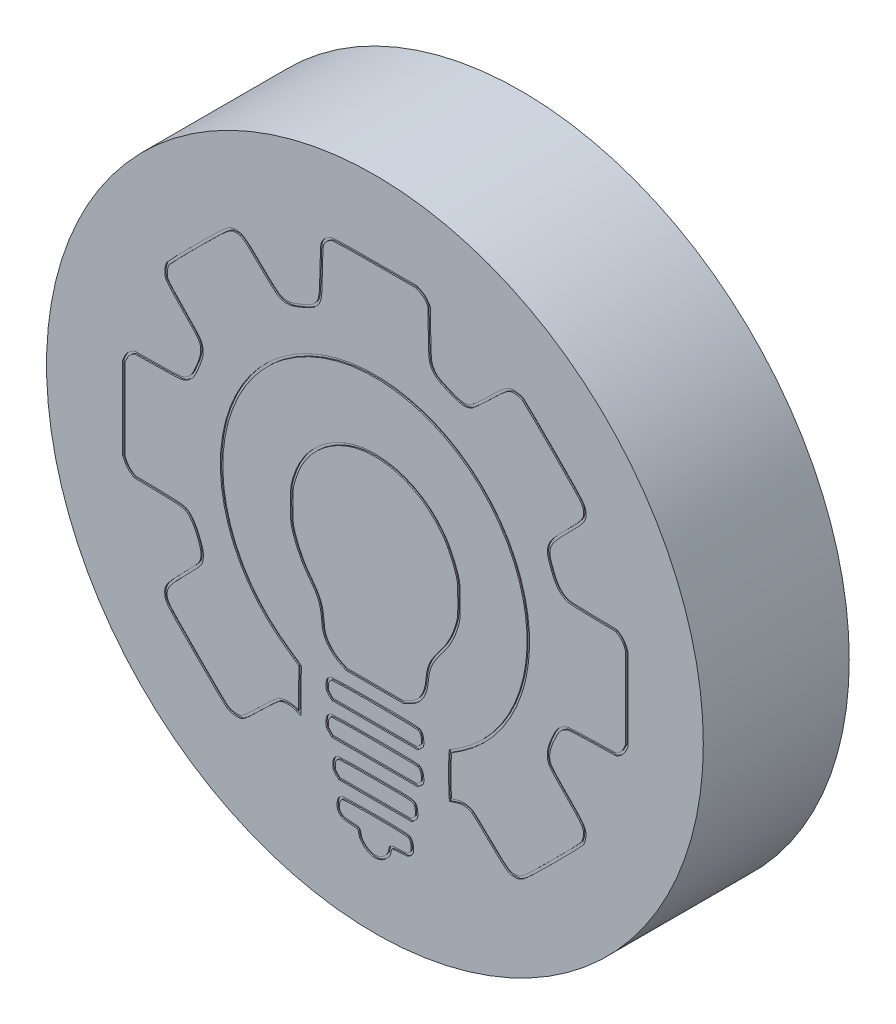
SolidWorks part; units mm, degrees
ref_plane "Front Plane" through (0, 0, 0) normal (0, 0, 1) x (1, 0, 0)
ref_plane "Top Plane" through (0, 0, 0) normal (0, 1, 0) x (1, 0, 0)
ref_plane "Right Plane" through (0, 0, 0) normal (1, 0, 0) x (0, 0, -1)
sketch "Sketch1" plane through (0, 0, 0) normal (0, 0, 1) x (1, 0, 0)
  circle A0 centre (0, 0) radius 25.025
  circle A1 centre (0, 0) radius 27
  dimension "D1" = 50.05
  dimension "D2" = 54
extrude "Boss-Extrude1" add sketch "Sketch1" along normal blind 10
sketch "Sketch2" plane through (0, 0, 10) normal (0, 0, 1) x (1, 0, 0)
  circle A0 centre (0, 0) radius 27
  circle A1 centre (0, 0) radius 27 construction
  point P8 (0, 0)
  circle M3 centre (0, 0) radius 27
  circle M4 centre (0, 0) radius 25.025
extrude "Boss-Extrude3" add sketch "Sketch2" along normal blind 2 contours M3 M4 | M4 region at (-26.2363, 0, 10) region at (0, 0, 10)
sketch "Sketch4" plane through (0, 0, 12) normal (0, 0, 1) x (1, 0, 0)
  line L0 (-17.8576, 4.6203) -> (-19.805, 4.585)
  line L1 (-19.805, 4.585) -> (-20.1013, 4.3874)
  line L2 (-20.574, 3.823) -> (-20.7433, 3.4561)
  line L3 (-20.7433, 3.4561) -> (-20.7433, 0.0624)
  line L4 (-20.7433, 0.0624) -> (-20.7433, -3.3243)
  line L5 (-20.7433, -3.3243) -> (-20.567, -3.6841)
  line L6 (-20.0942, -4.2415) -> (-19.805, -4.4461)
  line L7 (-19.805, -4.4461) -> (-17.8576, -4.4814)
  line L8 (-6.3994, -14.4086) -> (-6.0678, -14.5638)
  line L9 (-6.0678, -14.5638) -> (-6.0678, -12.7999)
  line L10 (17.9282, -4.4884) -> (19.8755, -4.4461)
  line L11 (19.8755, -4.4461) -> (20.1577, -4.2556)
  line L12 (20.6305, -3.6982) -> (20.8139, -3.3243)
  line L13 (20.8139, -3.3243) -> (20.8139, 0.0624)
  line L14 (20.8139, 0.0624) -> (20.8139, 3.4561)
  line L15 (20.8139, 3.4561) -> (20.6446, 3.823)
  line L16 (20.1718, 4.3874) -> (19.8755, 4.585)
  line L17 (19.8755, 4.585) -> (17.9282, 4.6203)
  line L18 (4.5861, 17.9976) -> (4.5508, 19.9097)
  line L19 (4.5508, 19.9097) -> (4.3603, 20.1919)
  line L20 (3.8029, 20.6646) -> (3.429, 20.8481)
  line L21 (3.429, 20.8481) -> (0.0423, 20.841)
  line L22 (-2.8363, -9.2298) -> (-2.3636, -9.4556)
  line L23 (-2.3636, -9.4556) -> (0, -9.4556)
  line L24 (0, -9.4556) -> (2.3636, -9.4556)
  line L25 (2.3636, -9.4556) -> (2.8363, -9.2298)
  line L26 (-3.7818, -11.9321) -> (-3.5419, -12.1719)
  line L27 (-3.5419, -12.1719) -> (-0.0071, -12.1719)
  line L28 (-0.0071, -12.1719) -> (3.5207, -12.1719)
  line L29 (3.5207, -12.1719) -> (3.7747, -11.9532)
  line L30 (-3.7818, -14.5629) -> (-3.5419, -14.8028)
  line L31 (-3.5419, -14.8028) -> (-0.0071, -14.8028)
  line L32 (-0.0071, -14.8028) -> (3.5207, -14.8028)
  line L33 (3.5207, -14.8028) -> (3.7747, -14.5841)
  line L34 (-3.2173, -17.2943) -> (-2.9774, -17.5342)
  line L35 (-2.9774, -17.5342) -> (0.0282, -17.5342)
  line L36 (0.0282, -17.5342) -> (3.0268, -17.5342)
  line L37 (3.0268, -17.5342) -> (3.2808, -17.3155)
  line L76 (-17.854, 4.4203) -> (-19.7428, 4.3861)
  line L77 (-19.7428, 4.3861) -> (-19.989, 4.2219)
  line L78 (-20.3932, 3.7376) -> (-20.5433, 3.4122)
  line L79 (-20.5433, 3.4122) -> (-20.5433, 0.0624)
  line L80 (-20.5433, 0.0624) -> (-20.5433, -3.2779)
  line L81 (-20.5433, -3.2779) -> (-20.3881, -3.5947)
  line L82 (-19.9817, -4.0761) -> (-19.7398, -4.2473)
  line L83 (-19.7398, -4.2473) -> (-17.854, -4.2814)
  line L84 (-6.3165, -14.2265) -> (-6.2678, -14.2493)
  line L85 (-6.2678, -14.2493) -> (-6.2678, -12.7999)
  line L86 (17.9238, -4.2885) -> (19.8124, -4.2474)
  line L87 (19.8124, -4.2474) -> (20.0471, -4.089)
  line L88 (20.4516, -3.6088) -> (20.6139, -3.2779)
  line L89 (20.6139, -3.2779) -> (20.6139, 0.0624)
  line L90 (20.6139, 0.0624) -> (20.6139, 3.4122)
  line L91 (20.6139, 3.4122) -> (20.4637, 3.7376)
  line L92 (20.0596, 4.2219) -> (19.8133, 4.3861)
  line L93 (19.8133, 4.3861) -> (17.9243, 4.4203)
  line L94 (4.3861, 17.9939) -> (4.352, 19.8468)
  line L95 (4.352, 19.8468) -> (4.1937, 20.0812)
  line L96 (3.7135, 20.4857) -> (3.3828, 20.648)
  line L97 (3.3828, 20.648) -> (0.0423, 20.641)
  line L98 (-2.7503, -9.0492) -> (-2.3183, -9.2556)
  line L99 (-2.3183, -9.2556) -> (0, -9.2556)
  line L100 (0, -9.2556) -> (2.3183, -9.2556)
  line L101 (2.3183, -9.2556) -> (2.7507, -9.0491)
  line L102 (-3.6404, -11.7906) -> (-3.459, -11.9719)
  line L103 (-3.459, -11.9719) -> (-0.0071, -11.9719)
  line L104 (-0.0071, -11.9719) -> (3.4465, -11.9719)
  line L105 (3.4465, -11.9719) -> (3.6424, -11.8032)
  line L106 (-3.6404, -14.4215) -> (-3.459, -14.6028)
  line L107 (-3.459, -14.6028) -> (-0.0071, -14.6028)
  line L108 (-0.0071, -14.6028) -> (3.4465, -14.6028)
  line L109 (3.4465, -14.6028) -> (3.6424, -14.4341)
  line L110 (-3.0759, -17.1529) -> (-2.8946, -17.3342)
  line L111 (-2.8946, -17.3342) -> (0.0282, -17.3342)
  line L112 (0.0282, -17.3342) -> (2.9526, -17.3342)
  line L113 (2.9526, -17.3342) -> (3.1485, -17.1655)
  spline S0 degree 3 poles (-3.5631, 20.7634) (-3.8876, 20.6435) (-4.1346, 20.4459) (-4.318, 20.1566) knots 0 0 0 0 1 1 1 1
  spline S1 degree 3 poles (-4.318, 20.1566) (-4.4732, 19.9026) (-4.4803, 19.825) (-4.5156, 17.9906) knots 0 0 0 0 1 1 1 1
  spline S2 degree 3 poles (-4.5156, 17.9906) (-4.5579, 15.888) (-4.5791, 15.7822) (-5.0236, 15.3377) knots 0 0 0 0 1 1 1 1
  spline S3 degree 3 poles (-5.0236, 15.3377) (-5.3128, 15.0413) (-6.5758, 14.4981) (-7.0767, 14.4416) knots 0 0 0 0 1 1 1 1
  spline S4 degree 3 poles (-7.0767, 14.4416) (-7.6976, 14.3781) (-7.9163, 14.5263) (-9.2851, 15.888) knots 0 0 0 0 1 1 1 1
  spline S5 degree 3 poles (-9.2851, 15.888) (-10.5622, 17.158) (-10.8797, 17.3838) (-11.3595, 17.3908) knots 0 0 0 0 1 1 1 1
  spline S6 degree 3 poles (-11.3595, 17.3908) (-12.0086, 17.3908) (-12.0297, 17.3767) (-14.5556, 14.865) knots 0 0 0 0 1 1 1 1
  spline S7 degree 3 poles (-14.5556, 14.865) (-15.868, 13.5526) (-17.0039, 12.3885) (-17.0815, 12.2615) knots 0 0 0 0 1 1 1 1
  spline S8 degree 3 poles (-17.0815, 12.2615) (-17.265, 11.9651) (-17.3285, 11.4148) (-17.2156, 11.0691) knots 0 0 0 0 1 1 1 1
  spline S9 degree 3 poles (-17.2156, 11.0691) (-17.145, 10.8645) (-16.7852, 10.4482) (-15.7974, 9.4463) knots 0 0 0 0 1 1 1 1
  spline S10 degree 3 poles (-15.7974, 9.4463) (-14.3933, 8.0211) (-14.3228, 7.9152) (-14.3228, 7.252) knots 0 0 0 0 1 1 1 1
  spline S11 degree 3 poles (-14.3228, 7.252) (-14.3228, 6.871) (-14.8378, 5.5657) (-15.113, 5.22) knots 0 0 0 0 1 1 1 1
  spline S12 degree 3 poles (-15.113, 5.22) (-15.233, 5.0859) (-15.4587, 4.8954) (-15.614, 4.8108) knots 0 0 0 0 1 1 1 1
  spline S13 degree 3 poles (-15.614, 4.8108) (-15.8962, 4.6697) (-16.0232, 4.6556) (-17.8576, 4.6203) knots 0 0 0 0 1 1 1 1
  spline S14 degree 3 poles (-20.1013, 4.3874) (-20.3059, 4.2463) (-20.4541, 4.077) (-20.574, 3.823) knots 0 0 0 0 1 1 1 1
  spline S15 degree 3 poles (-20.567, -3.6841) (-20.4541, -3.9099) (-20.2777, -4.1216) (-20.0942, -4.2415) knots 0 0 0 0 1 1 1 1
  spline S16 degree 3 poles (-17.8576, -4.4814) (-15.6563, -4.5237) (-15.5857, -4.5378) (-15.1412, -5.0529) knots 0 0 0 0 1 1 1 1
  spline S17 degree 3 poles (-15.1412, -5.0529) (-14.859, -5.3845) (-14.4216, -6.3441) (-14.3298, -6.8591) knots 0 0 0 0 1 1 1 1
  spline S18 degree 3 poles (-14.3298, -6.8591) (-14.2946, -7.0355) (-14.3016, -7.3036) (-14.3369, -7.5012) knots 0 0 0 0 1 1 1 1
  spline S19 degree 3 poles (-14.3369, -7.5012) (-14.4075, -7.8046) (-14.5133, -7.9386) (-15.7057, -9.1381) knots 0 0 0 0 1 1 1 1
  spline S20 degree 3 poles (-15.7057, -9.1381) (-17.0392, -10.4857) (-17.2791, -10.8243) (-17.2861, -11.3182) knots 0 0 0 0 1 1 1 1
  spline S21 degree 3 poles (-17.2861, -11.3182) (-17.2861, -11.9603) (-17.2579, -11.9956) (-14.7532, -14.5215) knots 0 0 0 0 1 1 1 1
  spline S22 degree 3 poles (-14.7532, -14.5215) (-13.4479, -15.8338) (-12.2837, -16.9697) (-12.1567, -17.0473) knots 0 0 0 0 1 1 1 1
  spline S23 degree 3 poles (-12.1567, -17.0473) (-11.8604, -17.2308) (-11.3101, -17.2943) (-10.9643, -17.1814) knots 0 0 0 0 1 1 1 1
  spline S24 degree 3 poles (-10.9643, -17.1814) (-10.7597, -17.1179) (-10.3576, -16.7651) (-9.3839, -15.8056) knots 0 0 0 0 1 1 1 1
  spline S25 degree 3 poles (-9.3839, -15.8056) (-8.6642, -15.1) (-7.9657, -14.458) (-7.8317, -14.3874) knots 0 0 0 0 1 1 1 1
  spline S26 degree 3 poles (-7.8317, -14.3874) (-7.4859, -14.204) (-6.8298, -14.2181) (-6.3994, -14.4086) knots 0 0 0 0 1 1 1 1
  spline S27 degree 3 poles (-6.0678, -12.7999) (-6.0678, -11.8333) (-6.0607, -11.0219) (-6.0537, -10.9866) knots 0 0 0 0 1 1 1 1
  spline S28 degree 3 poles (-6.0537, -10.9866) (-6.0537, -10.9584) (-6.4135, -10.6903) (-6.8651, -10.3869) knots 0 0 0 0 1 1 1 1
  spline S29 degree 3 poles (-6.8651, -10.3869) (-9.3133, -8.75) (-10.9785, -6.5769) (-11.8816, -3.8393) knots 0 0 0 0 1 1 1 1
  spline S30 degree 3 poles (-11.8816, -3.8393) (-13.5608, 1.2195) (-11.7969, 6.864) (-7.5424, 10.0672) knots 0 0 0 0 1 1 1 1
  spline S31 degree 3 poles (-7.5424, 10.0672) (-3.3796, 13.1928) (2.2366, 13.4327) (6.6675, 10.6669) knots 0 0 0 0 1 1 1 1
  spline S32 degree 3 poles (6.6675, 10.6669) (11.5006, 7.6542) (13.6807, 1.6217) (11.8886, -3.8111) knots 0 0 0 0 1 1 1 1
  spline S33 degree 3 poles (11.8886, -3.8111) (11.0067, -6.5063) (9.2992, -8.7571) (6.9427, -10.3375) knots 0 0 0 0 1 1 1 1
  spline S34 degree 3 poles (6.9427, -10.3375) (6.5476, -10.5986) (6.1948, -10.8243) (6.1454, -10.8384) knots 0 0 0 0 1 1 1 1
  spline S35 degree 3 poles (6.1454, -10.8384) (6.0184, -10.8808) (6.0254, -14.5426) (6.1524, -14.5215) knots 0 0 0 0 1 1 1 1
  spline S36 degree 3 poles (6.1524, -14.5215) (6.2018, -14.5144) (6.4347, -14.4368) (6.6675, -14.3592) knots 0 0 0 0 1 1 1 1
  spline S37 degree 3 poles (6.6675, -14.3592) (7.1261, -14.1898) (7.5424, -14.211) (7.9375, -14.4086) knots 0 0 0 0 1 1 1 1
  spline S38 degree 3 poles (7.9375, -14.4086) (8.0504, -14.4721) (8.7207, -15.0859) (9.4192, -15.7773) knots 0 0 0 0 1 1 1 1
  spline S39 degree 3 poles (9.4192, -15.7773) (10.7033, -17.0473) (10.9855, -17.252) (11.4371, -17.252) knots 0 0 0 0 1 1 1 1
  spline S40 degree 3 poles (11.4371, -17.252) (12.065, -17.252) (12.1144, -17.2167) (14.6262, -14.719) knots 0 0 0 0 1 1 1 1
  spline S41 degree 3 poles (14.6262, -14.719) (15.9385, -13.4137) (17.0745, -12.2496) (17.1521, -12.1226) knots 0 0 0 0 1 1 1 1
  spline S42 degree 3 poles (17.1521, -12.1226) (17.2297, -12.0026) (17.3073, -11.7416) (17.3355, -11.544) knots 0 0 0 0 1 1 1 1
  spline S43 degree 3 poles (17.3355, -11.544) (17.4131, -10.8878) (17.272, -10.6762) (15.8538, -9.2509) knots 0 0 0 0 1 1 1 1
  spline S44 degree 3 poles (15.8538, -9.2509) (15.106, -8.5031) (14.5415, -7.8751) (14.478, -7.734) knots 0 0 0 0 1 1 1 1
  spline S45 degree 3 poles (14.478, -7.734) (14.2946, -7.2966) (14.344, -6.845) (14.6403, -6.1042) knots 0 0 0 0 1 1 1 1
  spline S46 degree 3 poles (14.6403, -6.1042) (15.0354, -5.1305) (15.2471, -4.8553) (15.8045, -4.6084) knots 0 0 0 0 1 1 1 1
  spline S47 degree 3 poles (15.8045, -4.6084) (15.9103, -4.559) (16.7287, -4.5096) (17.9282, -4.4884) knots 0 0 0 0 1 1 1 1
  spline S48 degree 3 poles (20.1577, -4.2556) (20.3412, -4.1357) (20.5105, -3.9381) (20.6305, -3.6982) knots 0 0 0 0 1 1 1 1
  spline S49 degree 3 poles (20.6446, 3.823) (20.5246, 4.077) (20.3765, 4.2463) (20.1718, 4.3874) knots 0 0 0 0 1 1 1 1
  spline S50 degree 3 poles (17.9282, 4.6203) (16.0937, 4.6556) (15.9667, 4.6697) (15.6845, 4.8108) knots 0 0 0 0 1 1 1 1
  spline S51 degree 3 poles (15.6845, 4.8108) (15.2612, 5.0366) (15.0142, 5.3823) (14.6826, 6.2078) knots 0 0 0 0 1 1 1 1
  spline S52 degree 3 poles (14.6826, 6.2078) (14.1393, 7.5766) (14.2311, 7.8306) (15.9103, 9.4886) knots 0 0 0 0 1 1 1 1
  spline S53 degree 3 poles (15.9103, 9.4886) (17.1168, 10.681) (17.3496, 10.9985) (17.3567, 11.4571) knots 0 0 0 0 1 1 1 1
  spline S54 degree 3 poles (17.3567, 11.4571) (17.3567, 12.0992) (17.3285, 12.1345) (14.8237, 14.6603) knots 0 0 0 0 1 1 1 1
  spline S55 degree 3 poles (14.8237, 14.6603) (13.5185, 15.9727) (12.3543, 17.1086) (12.2273, 17.1862) knots 0 0 0 0 1 1 1 1
  spline S56 degree 3 poles (12.2273, 17.1862) (12.1073, 17.2638) (11.8463, 17.3415) (11.6487, 17.3697) knots 0 0 0 0 1 1 1 1
  spline S57 degree 3 poles (11.6487, 17.3697) (10.9926, 17.4473) (10.7668, 17.3062) (9.3486, 15.9021) knots 0 0 0 0 1 1 1 1
  spline S58 degree 3 poles (9.3486, 15.9021) (8.5725, 15.1401) (7.9728, 14.6039) (7.8105, 14.5333) knots 0 0 0 0 1 1 1 1
  spline S59 degree 3 poles (7.8105, 14.5333) (7.3801, 14.357) (7.0203, 14.3993) (6.1807, 14.745) knots 0 0 0 0 1 1 1 1
  spline S60 degree 3 poles (6.1807, 14.745) (5.2564, 15.126) (5.0024, 15.3024) (4.7907, 15.7469) knots 0 0 0 0 1 1 1 1
  spline S61 degree 3 poles (4.7907, 15.7469) (4.6284, 16.0715) (4.6214, 16.1702) (4.5861, 17.9976) knots 0 0 0 0 1 1 1 1
  spline S62 degree 3 poles (4.3603, 20.1919) (4.2404, 20.3753) (4.0428, 20.5447) (3.8029, 20.6646) knots 0 0 0 0 1 1 1 1
  spline S63 degree 3 poles (0.0423, 20.841) (-2.1661, 20.841) (-3.429, 20.8128) (-3.5631, 20.7634) knots 0 0 0 0 1 1 1 1
  spline S64 degree 3 poles (-1.0231, 7.0827) (-2.8998, 6.8146) (-4.7413, 5.6363) (-5.8279, 4.0135) knots 0 0 0 0 1 1 1 1
  spline S65 degree 3 poles (-5.8279, 4.0135) (-6.2653, 3.3503) (-6.4911, 2.8705) (-6.7522, 2.0168) knots 0 0 0 0 1 1 1 1
  spline S66 degree 3 poles (-6.7522, 2.0168) (-6.9286, 1.4523) (-6.9427, 1.3183) (-6.9427, 0.1047) knots 0 0 0 0 1 1 1 1
  spline S67 degree 3 poles (-6.9427, 0.1047) (-6.9427, -1.1229) (-6.9286, -1.2429) (-6.7522, -1.8285) knots 0 0 0 0 1 1 1 1
  spline S68 degree 3 poles (-6.7522, -1.8285) (-6.5052, -2.6258) (-5.9619, -3.6841) (-5.5174, -4.2344) knots 0 0 0 0 1 1 1 1
  spline S69 degree 3 poles (-5.5174, -4.2344) (-4.6849, -5.2787) (-4.4732, -5.7584) (-4.3815, -6.8591) knots 0 0 0 0 1 1 1 1
  spline S70 degree 3 poles (-4.3815, -6.8591) (-4.3392, -7.4165) (-4.2827, -7.6634) (-4.1346, -7.9668) knots 0 0 0 0 1 1 1 1
  spline S71 degree 3 poles (-4.1346, -7.9668) (-3.8664, -8.5101) (-3.4008, -8.9617) (-2.8363, -9.2298) knots 0 0 0 0 1 1 1 1
  spline S72 degree 3 poles (2.8363, -9.2298) (3.7959, -8.7782) (4.2827, -8.0374) (4.3886, -6.8662) knots 0 0 0 0 1 1 1 1
  spline S73 degree 3 poles (4.3886, -6.8662) (4.4873, -5.7937) (4.699, -5.3351) (5.6797, -4.0933) knots 0 0 0 0 1 1 1 1
  spline S74 degree 3 poles (5.6797, -4.0933) (6.1454, -3.5007) (6.5546, -2.6963) (6.8157, -1.8356) knots 0 0 0 0 1 1 1 1
  spline S75 degree 3 poles (6.8157, -1.8356) (6.9991, -1.2358) (7.0132, -1.1229) (7.0132, 0.1047) knots 0 0 0 0 1 1 1 1
  spline S76 degree 3 poles (7.0132, 0.1047) (7.0132, 1.3253) (6.9991, 1.4523) (6.8227, 2.0309) knots 0 0 0 0 1 1 1 1
  spline S77 degree 3 poles (6.8227, 2.0309) (6.5899, 2.7858) (6.1242, 3.7313) (5.6938, 4.3098) knots 0 0 0 0 1 1 1 1
  spline S78 degree 3 poles (5.6938, 4.3098) (4.1698, 6.3771) (1.5663, 7.4496) (-1.0231, 7.0827) knots 0 0 0 0 1 1 1 1
  spline S79 degree 3 poles (-3.6336, -10.5633) (-3.9088, -10.7114) (-4.0217, -10.9231) (-4.0217, -11.3112) knots 0 0 0 0 1 1 1 1
  spline S80 degree 3 poles (-4.0217, -11.3112) (-4.0217, -11.6498) (-3.9934, -11.7204) (-3.7818, -11.9321) knots 0 0 0 0 1 1 1 1
  spline S81 degree 3 poles (3.7747, -11.9532) (3.9934, -11.7557) (4.0217, -11.6992) (4.0217, -11.3817) knots 0 0 0 0 1 1 1 1
  spline S82 degree 3 poles (4.0217, -11.3817) (4.0217, -10.9654) (3.8876, -10.6762) (3.6336, -10.5633) knots 0 0 0 0 1 1 1 1
  spline S83 degree 3 poles (3.6336, -10.5633) (3.3867, -10.4504) (-3.429, -10.4433) (-3.6336, -10.5633) knots 0 0 0 0 1 1 1 1
  spline S84 degree 3 poles (-3.6336, -13.1941) (-3.9088, -13.3423) (-4.0217, -13.554) (-4.0217, -13.942) knots 0 0 0 0 1 1 1 1
  spline S85 degree 3 poles (-4.0217, -13.942) (-4.0217, -14.2807) (-3.9934, -14.3513) (-3.7818, -14.5629) knots 0 0 0 0 1 1 1 1
  spline S86 degree 3 poles (3.7747, -14.5841) (3.9934, -14.3865) (4.0217, -14.3301) (4.0217, -14.0126) knots 0 0 0 0 1 1 1 1
  spline S87 degree 3 poles (4.0217, -14.0126) (4.0217, -13.6104) (3.8664, -13.3) (3.6195, -13.1871) knots 0 0 0 0 1 1 1 1
  spline S88 degree 3 poles (3.6195, -13.1871) (3.3796, -13.0813) (-3.4361, -13.0813) (-3.6336, -13.1941) knots 0 0 0 0 1 1 1 1
  spline S89 degree 3 poles (-3.0692, -15.9255) (-3.3443, -16.0737) (-3.4572, -16.2853) (-3.4572, -16.6734) knots 0 0 0 0 1 1 1 1
  spline S90 degree 3 poles (-3.4572, -16.6734) (-3.4572, -17.0121) (-3.429, -17.0826) (-3.2173, -17.2943) knots 0 0 0 0 1 1 1 1
  spline S91 degree 3 poles (3.2808, -17.3155) (3.4996, -17.1179) (3.5278, -17.0544) (3.5278, -16.751) knots 0 0 0 0 1 1 1 1
  spline S92 degree 3 poles (3.5278, -16.751) (3.5278, -16.5676) (3.4925, -16.3277) (3.4431, -16.2289) knots 0 0 0 0 1 1 1 1
  spline S93 degree 3 poles (3.4431, -16.2289) (3.2667, -15.8479) (3.2173, -15.8408) (0.0212, -15.8408) knots 0 0 0 0 1 1 1 1
  spline S94 degree 3 poles (0.0212, -15.8408) (-1.9897, -15.8479) (-2.9704, -15.8691) (-3.0692, -15.9255) knots 0 0 0 0 1 1 1 1
  spline S95 degree 3 poles (-2.7376, -18.6137) (-2.9845, -18.7548) (-3.1044, -18.9735) (-3.1115, -19.3122) knots 0 0 0 0 1 1 1 1
  spline S96 degree 3 poles (-3.1115, -19.3122) (-3.1256, -19.6508) (-3.0551, -19.8272) (-2.8222, -20.0389) knots 0 0 0 0 1 1 1 1
  spline S97 degree 3 poles (-2.8222, -20.0389) (-2.7023, -20.1518) (-2.5329, -20.1871) (-2.0249, -20.2153) knots 0 0 0 0 1 1 1 1
  spline S98 degree 3 poles (-2.0249, -20.2153) (-1.4464, -20.2435) (-1.3758, -20.2647) (-1.3547, -20.3917) knots 0 0 0 0 1 1 1 1
  spline S99 degree 3 poles (-1.3547, -20.3917) (-1.3053, -20.7515) (-1.2559, -20.8644) (-1.0372, -21.1043) knots 0 0 0 0 1 1 1 1
  spline S100 degree 3 poles (-1.0372, -21.1043) (-0.4516, -21.7816) (0.4516, -21.7816) (1.0372, -21.1043) knots 0 0 0 0 1 1 1 1
  spline S101 degree 3 poles (1.0372, -21.1043) (1.2559, -20.8644) (1.3053, -20.7515) (1.3547, -20.3917) knots 0 0 0 0 1 1 1 1
  spline S102 degree 3 poles (1.3547, -20.3917) (1.3758, -20.2647) (1.4464, -20.2506) (2.0602, -20.2153) knots 0 0 0 0 1 1 1 1
  spline S103 degree 3 poles (2.0602, -20.2153) (2.6952, -20.18) (2.7587, -20.1659) (2.9563, -19.9754) knots 0 0 0 0 1 1 1 1
  spline S104 degree 3 poles (2.9563, -19.9754) (3.1397, -19.799) (3.175, -19.7143) (3.175, -19.4321) knots 0 0 0 0 1 1 1 1
  spline S105 degree 3 poles (3.175, -19.4321) (3.175, -19.0088) (3.0621, -18.7477) (2.8152, -18.6207) knots 0 0 0 0 1 1 1 1
  spline S106 degree 3 poles (2.8152, -18.6207) (2.5471, -18.4867) (-2.4906, -18.4796) (-2.7376, -18.6137) knots 0 0 0 0 1 1 1 1
  spline S107 degree 1 poles (-19.989, 4.2219) (-20.3932, 3.7376) knots 0 0 1 1 construction
  spline S108 degree 1 poles (-20.3881, -3.5947) (-19.9817, -4.0761) knots 0 0 1 1 construction
  spline S109 degree 1 poles (-17.854, -4.2814) (-14.9894, -4.9227) knots 0 0 1 1 construction
  spline S110 degree 1 poles (-14.9894, -4.9227) (-14.1333, -6.822) knots 0 0 1 1 construction
  spline S111 degree 1 poles (-14.1333, -6.822) (-14.1409, -7.5414) knots 0 0 1 1 construction
  spline S112 degree 1 poles (-14.1409, -7.5414) (-15.5637, -9.2789) knots 0 0 1 1 construction
  spline S113 degree 1 poles (-15.5637, -9.2789) (-17.0861, -11.3197) knots 0 0 1 1 construction
  spline S114 degree 1 poles (-17.0861, -11.3197) (-14.6113, -14.3805) knots 0 0 1 1 construction
  spline S115 degree 1 poles (-14.6113, -14.3805) (-12.0501, -16.8781) knots 0 0 1 1 construction
  spline S116 degree 1 poles (-12.0501, -16.8781) (-11.025, -16.9908) knots 0 0 1 1 construction
  spline S117 degree 1 poles (-11.025, -16.9908) (-9.5241, -15.6629) knots 0 0 1 1 construction
  spline S118 degree 1 poles (-9.5241, -15.6629) (-7.9252, -14.2106) knots 0 0 1 1 construction
  spline S119 degree 1 poles (-7.9252, -14.2106) (-6.3165, -14.2265) knots 0 0 1 1 construction
  spline S120 degree 1 poles (-6.2678, -12.7999) (-6.2573, -11.0672) knots 0 0 1 1 construction
  spline S121 degree 1 poles (-6.2573, -11.0672) (-6.9764, -10.553) knots 0 0 1 1 construction
  spline S122 degree 1 poles (-6.9764, -10.553) (-12.0714, -3.9022) knots 0 0 1 1 construction
  spline S123 degree 1 poles (-12.0714, -3.9022) (-7.6626, 10.227) knots 0 0 1 1 construction
  spline S124 degree 1 poles (-7.6626, 10.227) (6.7734, 10.8366) knots 0 0 1 1 construction
  spline S125 degree 1 poles (6.7734, 10.8366) (12.0786, -3.8735) knots 0 0 1 1 construction
  spline S126 degree 1 poles (12.0786, -3.8735) (7.0535, -10.504) knots 0 0 1 1 construction
  spline S127 degree 1 poles (7.0535, -10.504) (6.3095, -10.9791) knots 0 0 1 1 construction
  spline S128 degree 1 poles (6.3095, -10.9791) (6.3008, -14.2697) knots 0 0 1 1 construction
  spline S129 degree 1 poles (6.3008, -14.2697) (6.6013, -14.1704) knots 0 0 1 1 construction
  spline S130 degree 1 poles (6.6013, -14.1704) (8.0313, -14.2319) knots 0 0 1 1 construction
  spline S131 degree 1 poles (8.0313, -14.2319) (9.5598, -15.6352) knots 0 0 1 1 construction
  spline S132 degree 1 poles (9.5598, -15.6352) (11.4371, -17.052) knots 0 0 1 1 construction
  spline S133 degree 1 poles (11.4371, -17.052) (14.4851, -14.5772) knots 0 0 1 1 construction
  spline S134 degree 1 poles (14.4851, -14.5772) (16.9828, -12.0161) knots 0 0 1 1 construction
  spline S135 degree 1 poles (16.9828, -12.0161) (17.1372, -11.5181) knots 0 0 1 1 construction
  spline S136 degree 1 poles (17.1372, -11.5181) (15.7122, -9.3922) knots 0 0 1 1 construction
  spline S137 degree 1 poles (15.7122, -9.3922) (14.2946, -7.8137) knots 0 0 1 1 construction
  spline S138 degree 1 poles (14.2946, -7.8137) (14.4548, -6.0294) knots 0 0 1 1 construction
  spline S139 degree 1 poles (14.4548, -6.0294) (15.7222, -4.4261) knots 0 0 1 1 construction
  spline S140 degree 1 poles (15.7222, -4.4261) (17.9238, -4.2885) knots 0 0 1 1 construction
  spline S141 degree 1 poles (20.0471, -4.089) (20.4516, -3.6088) knots 0 0 1 1 construction
  spline S142 degree 1 poles (20.4637, 3.7376) (20.0596, 4.2219) knots 0 0 1 1 construction
  spline S143 degree 1 poles (17.9243, 4.4203) (15.5927, 4.6331) knots 0 0 1 1 construction
  spline S144 degree 1 poles (15.5927, 4.6331) (14.4969, 6.1336) knots 0 0 1 1 construction
  spline S145 degree 1 poles (14.4969, 6.1336) (15.7697, 9.6309) knots 0 0 1 1 construction
  spline S146 degree 1 poles (15.7697, 9.6309) (17.1567, 11.4587) knots 0 0 1 1 construction
  spline S147 degree 1 poles (17.1567, 11.4587) (14.6818, 14.5194) knots 0 0 1 1 construction
  spline S148 degree 1 poles (14.6818, 14.5194) (12.1208, 17.0169) knots 0 0 1 1 construction
  spline S149 degree 1 poles (12.1208, 17.0169) (11.6228, 17.1714) knots 0 0 1 1 construction
  spline S150 degree 1 poles (11.6228, 17.1714) (9.489, 15.7597) knots 0 0 1 1 construction
  spline S151 degree 1 poles (9.489, 15.7597) (7.8883, 14.3491) knots 0 0 1 1 construction
  spline S152 degree 1 poles (7.8883, 14.3491) (6.1045, 14.5601) knots 0 0 1 1 construction
  spline S153 degree 1 poles (6.1045, 14.5601) (4.611, 15.6592) knots 0 0 1 1 construction
  spline S154 degree 1 poles (4.611, 15.6592) (4.3861, 17.9939) knots 0 0 1 1 construction
  spline S155 degree 1 poles (4.1937, 20.0812) (3.7135, 20.4857) knots 0 0 1 1 construction
  spline S156 degree 1 poles (0.0423, 20.641) (-3.4992, 20.5738) knots 0 0 1 1 construction
  spline S157 degree 1 poles (-3.4992, 20.5738) (-4.1482, 20.0509) knots 0 0 1 1 construction
  spline S158 degree 1 poles (-4.1482, 20.0509) (-4.3156, 17.9866) knots 0 0 1 1 construction
  spline S159 degree 1 poles (-4.3156, 17.9866) (-4.8814, 15.197) knots 0 0 1 1 construction
  spline S160 degree 1 poles (-4.8814, 15.197) (-7.0554, 14.2428) knots 0 0 1 1 construction
  spline S161 degree 1 poles (-7.0554, 14.2428) (-9.4262, 15.7462) knots 0 0 1 1 construction
  spline S162 degree 1 poles (-9.4262, 15.7462) (-11.361, 17.1908) knots 0 0 1 1 construction
  spline S163 degree 1 poles (-11.361, 17.1908) (-14.4144, 14.7233) knots 0 0 1 1 construction
  spline S164 degree 1 poles (-14.4144, 14.7233) (-16.9123, 12.1549) knots 0 0 1 1 construction
  spline S165 degree 1 poles (-16.9123, 12.1549) (-17.026, 11.1329) knots 0 0 1 1 construction
  spline S166 degree 1 poles (-17.026, 11.1329) (-15.655, 9.5867) knots 0 0 1 1 construction
  spline S167 degree 1 poles (-15.655, 9.5867) (-14.1228, 7.252) knots 0 0 1 1 construction
  spline S168 degree 1 poles (-14.1228, 7.252) (-14.9601, 5.0909) knots 0 0 1 1 construction
  spline S169 degree 1 poles (-14.9601, 5.0909) (-15.5213, 4.6335) knots 0 0 1 1 construction
  spline S170 degree 1 poles (-15.5213, 4.6335) (-17.854, 4.4203) knots 0 0 1 1 construction
  spline S171 degree 3 poles (-19.989, 4.2219) (-20.0319, 4.1923) (-20.1163, 4.1267) (-20.2192, 4.0206) (-20.3099, 3.8978) (-20.3682, 3.7904) (-20.3932, 3.7376) knots 0.002323 0.002323 0.002323 0.002323 0.251742 0.501161 0.750581 1 1 1 1
  spline S172 degree 3 poles (-20.3881, -3.5947) (-20.363, -3.6448) (-20.3067, -3.7417) (-20.2049, -3.8781) (-20.0918, -3.9953) (-20.0211, -4.0504) (-19.9817, -4.0761) knots 0 0 0 0 0.25139 0.502779 0.754169 1.005559 1.005559 1.005559 1.005559
  spline S173 degree 3 poles (-17.854, -4.2814) (-17.7244, -4.2839) (-17.4538, -4.2892) (-17.0029, -4.2994) (-16.534, -4.3146) (-16.111, -4.3432) (-15.6809, -4.404) (-15.304, -4.5609) (-15.0925, -4.8032) (-14.9894, -4.9227) knots -0.000034 -0.000034 -0.000034 -0.000034 0.062489 0.125013 0.250059 0.375105 0.500152 0.750245 1.000338 1.000338 1.000338 1.000338
  spline S174 degree 3 poles (-14.9894, -4.9227) (-14.9436, -4.9766) (-14.8652, -5.0844) (-14.6914, -5.3691) (-14.4773, -5.7943) (-14.2524, -6.3571) (-14.1628, -6.6573) (-14.1333, -6.822) knots -0.000527 -0.000527 -0.000527 -0.000527 0.124393 0.249313 0.499154 0.748994 0.998835 0.998835 0.998835 0.998835
  spline S175 degree 3 poles (-14.1333, -6.822) (-14.122, -6.8791) (-14.1088, -6.9924) (-14.1045, -7.1793) (-14.1152, -7.3686) (-14.1305, -7.4833) (-14.1409, -7.5414) knots 0.003226 0.003226 0.003226 0.003226 0.25457 0.505915 0.757259 1.008604 1.008604 1.008604 1.008604
  spline S176 degree 3 poles (-14.1409, -7.5414) (-14.1619, -7.6318) (-14.2122, -7.7972) (-14.3793, -8.0379) (-14.6058, -8.2954) (-14.8383, -8.5424) (-15.0974, -8.808) (-15.3454, -9.0591) (-15.4928, -9.2076) (-15.5637, -9.2789) knots -0.005543 -0.005543 -0.005543 -0.005543 0.245831 0.497206 0.622893 0.74858 0.874267 0.937111 0.999954 0.999954 0.999954 0.999954
  spline S177 degree 3 poles (-15.5637, -9.2789) (-15.6427, -9.3587) (-15.806, -9.5245) (-16.0852, -9.8118) (-16.3807, -10.1244) (-16.6485, -10.4272) (-16.9062, -10.7551) (-17.0599, -11.0361) (-17.0846, -11.2203) (-17.0861, -11.3197) knots 0.000041 0.000041 0.000041 0.000041 0.062471 0.124902 0.249763 0.374624 0.499485 0.749207 0.998929 0.998929 0.998929 0.998929
  spline S178 degree 3 poles (-17.0861, -11.3197) (-17.0861, -11.3867) (-17.0844, -11.5355) (-17.0592, -11.6701) (-16.9879, -11.8353) (-16.8223, -12.0734) (-16.5312, -12.4124) (-16.0911, -12.8797) (-15.5728, -13.4093) (-15.0654, -13.9225) (-14.7582, -14.2323) (-14.6113, -14.3805) knots 0.000773 0.000773 0.000773 0.000773 0.125675 0.250576 0.375478 0.50038 0.625281 0.750183 0.875084 0.937535 0.999986 0.999986 0.999986 0.999986
  spline S179 degree 3 poles (-14.6113, -14.3805) (-14.3067, -14.6867) (-13.6667, -15.3261) (-13.0066, -15.9757) (-12.5759, -16.3931) (-12.3149, -16.6415) (-12.1607, -16.7842) (-12.074, -16.8594) (-12.0611, -16.8702) (-12.0501, -16.8781) knots 0.000027 0.000027 0.000027 0.000027 0.244111 0.488195 0.610236 0.732278 0.85432 0.915341 0.976362 0.976362 0.976362 0.976362
  spline S180 degree 3 poles (-12.0501, -16.8781) (-11.9834, -16.9192) (-11.8494, -16.974) (-11.556, -17.0367) (-11.2541, -17.0412) (-11.1028, -17.0162) (-11.025, -16.9908) knots 0.002003 0.002003 0.002003 0.002003 0.251839 0.501675 0.751511 1.001347 1.001347 1.001347 1.001347
  spline S181 degree 3 poles (-11.025, -16.9908) (-11.0073, -16.9853) (-10.9841, -16.9752) (-10.8573, -16.8986) (-10.6225, -16.7104) (-10.2529, -16.3709) (-9.8754, -16.0078) (-9.6367, -15.7739) (-9.5241, -15.6629) knots -0.002287 -0.002287 -0.002287 -0.002287 0.123007 0.248301 0.498888 0.749476 0.87477 1.000063 1.000063 1.000063 1.000063
  spline S182 degree 3 poles (-9.5241, -15.6629) (-9.3489, -15.4912) (-8.9825, -15.1373) (-8.5061, -14.6923) (-8.1964, -14.4159) (-8.0233, -14.2751) (-7.9624, -14.2302) (-7.9252, -14.2106) knots -0.000086 -0.000086 -0.000086 -0.000086 0.249847 0.499779 0.749712 0.874679 0.999645 0.999645 0.999645 0.999645
  spline S183 degree 3 poles (-7.9252, -14.2106) (-7.8113, -14.1502) (-7.5674, -14.0766) (-7.1446, -14.0447) (-6.7091, -14.0913) (-6.4437, -14.1702) (-6.3165, -14.2265) knots 0.000189 0.000189 0.000189 0.000189 0.250515 0.500841 0.751167 1.001494 1.001494 1.001494 1.001494
  spline S184 degree 3 poles (-6.2678, -12.7999) (-6.2678, -12.6085) (-6.2672, -12.2098) (-6.2648, -11.7068) (-6.262, -11.3729) (-6.2593, -11.169) (-6.2581, -11.1043) (-6.2573, -11.0672) knots 0 0 0 0 0.206567 0.413133 0.6197 0.722983 0.826266 0.826266 0.826266 0.826266
  spline S185 degree 3 poles (-6.2573, -11.0672) (-6.2956, -11.0361) (-6.3621, -10.985) (-6.536, -10.8573) (-6.7384, -10.7147) (-6.8988, -10.6052) (-6.9764, -10.553) knots 0.27751 0.27751 0.27751 0.27751 0.458097 0.638685 0.819273 0.99986 0.99986 0.99986 0.99986
  spline S186 degree 3 poles (-6.9764, -10.553) (-7.5808, -10.149) (-8.7469, -9.2354) (-10.1592, -7.682) (-11.2854, -5.9214) (-11.8473, -4.5815) (-12.0714, -3.9022) knots 0.000025 0.000025 0.000025 0.000025 0.250014 0.500002 0.749991 0.999979 0.999979 0.999979 0.999979
  spline S187 degree 3 poles (-12.0714, -3.9022) (-12.2822, -3.2671) (-12.6031, -1.9523) (-12.8135, 0.6761) (-12.3171, 3.9287) (-10.8751, 6.8855) (-9.2077, 8.9267) (-8.1968, 9.8249) (-7.6626, 10.227) knots 0.000011 0.000011 0.000011 0.000011 0.125011 0.250011 0.50001 0.750009 0.875009 1.000008 1.000008 1.000008 1.000008
  spline S188 degree 3 poles (-7.6626, 10.227) (-7.1409, 10.6187) (-6.0277, 11.3284) (-3.6829, 12.3608) (-0.5551, 12.9641) (2.6154, 12.6276) (5.0448, 11.7967) (6.2183, 11.183) (6.7734, 10.8366) knots -0.000008 -0.000008 -0.000008 -0.000008 0.124992 0.249993 0.499994 0.749995 0.874996 0.999996 0.999996 0.999996 0.999996
  spline S189 degree 3 poles (6.7734, 10.8366) (7.3791, 10.459) (8.5348, 9.5901) (10.4582, 7.5449) (12.1619, 4.4806) (12.809, 1.0303) (12.6368, -1.7799) (12.3031, -3.193) (12.0786, -3.8735) knots 0.000004 0.000004 0.000004 0.000004 0.125001 0.249999 0.499995 0.749991 0.874988 0.999986 0.999986 0.999986 0.999986
  spline S190 degree 3 poles (12.0786, -3.8735) (11.8576, -4.5489) (11.3009, -5.8741) (10.174, -7.6485) (8.7696, -9.2131) (7.6439, -10.108) (7.0535, -10.504) knots 0.000028 0.000028 0.000028 0.000028 0.250041 0.500054 0.750068 1.000081 1.000081 1.000081 1.000081
  spline S191 degree 3 poles (7.0535, -10.504) (6.9768, -10.5547) (6.8177, -10.6592) (6.6101, -10.7936) (6.4284, -10.9082) (6.3536, -10.9539) (6.3095, -10.9791) knots -0.000485 -0.000485 -0.000485 -0.000485 0.199236 0.398958 0.598679 0.7984 0.7984 0.7984 0.7984
  spline S192 degree 3 poles (6.3095, -10.9791) (6.3045, -11.0135) (6.2979, -11.0732) (6.2823, -11.2686) (6.268, -11.5801) (6.2569, -12.0396) (6.2526, -12.5435) (6.2548, -13.0569) (6.2636, -13.5447) (6.276, -13.8967) (6.2896, -14.1338) (6.2963, -14.2219) (6.3008, -14.2697) knots 0.098872 0.098872 0.098872 0.098872 0.1454 0.191929 0.284986 0.378043 0.4711 0.564157 0.657214 0.750271 0.796799 0.843328 0.843328 0.843328 0.843328
  spline S193 degree 3 poles (6.3008, -14.2697) (6.3237, -14.2623) (6.3682, -14.2478) (6.4433, -14.223) (6.5211, -14.1971) (6.5747, -14.1793) (6.6013, -14.1704) knots 0.536874 0.536874 0.536874 0.536874 0.651594 0.766314 0.881035 0.995755 0.995755 0.995755 0.995755
  spline S194 degree 3 poles (6.6013, -14.1704) (6.722, -14.126) (6.977, -14.0562) (7.3402, -14.0338) (7.695, -14.0884) (7.9232, -14.1778) (8.0313, -14.2319) knots 0.002041 0.002041 0.002041 0.002041 0.25245 0.50286 0.753269 1.003679 1.003679 1.003679 1.003679
  spline S195 degree 3 poles (8.0313, -14.2319) (8.0628, -14.2496) (8.1133, -14.2865) (8.272, -14.4179) (8.5658, -14.6815) (9.0278, -15.1149) (9.3883, -15.4654) (9.5598, -15.6352) knots -0.012546 -0.012546 -0.012546 -0.012546 0.11402 0.240587 0.493719 0.746852 0.999985 0.999985 0.999985 0.999985
  spline S196 degree 3 poles (9.5598, -15.6352) (9.6359, -15.7104) (9.794, -15.8662) (10.0662, -16.1313) (10.3604, -16.4107) (10.6417, -16.6616) (10.9421, -16.8998) (11.1869, -17.034) (11.3499, -17.052) (11.4371, -17.052) knots 0.000008 0.000008 0.000008 0.000008 0.062508 0.125007 0.250006 0.375005 0.500004 0.750002 1 1 1 1
  spline S197 degree 3 poles (11.4371, -17.052) (11.5027, -17.052) (11.6481, -17.0501) (11.7806, -17.0247) (11.9457, -16.9527) (12.1841, -16.7862) (12.5231, -16.4947) (12.9899, -16.0547) (13.518, -15.537) (14.0292, -15.0304) (14.3376, -14.7239) (14.4851, -14.5772) knots 0 0 0 0 0.125 0.25 0.375 0.499999 0.624999 0.749999 0.874999 0.937499 0.999999 0.999999 0.999999 0.999999
  spline S198 degree 3 poles (14.4851, -14.5772) (14.7912, -14.2728) (15.4302, -13.6332) (16.0795, -12.9734) (16.4969, -12.5427) (16.7454, -12.2816) (16.8883, -12.1273) (16.9637, -12.0403) (16.9747, -12.0271) (16.9828, -12.0161) knots 0.000002 0.000002 0.000002 0.000002 0.243936 0.48787 0.609837 0.731803 0.85377 0.914754 0.975737 0.975737 0.975737 0.975737
  spline S199 degree 3 poles (16.9828, -12.0161) (16.9993, -11.9905) (17.0208, -11.9466) (17.0722, -11.8083) (17.1126, -11.6564) (17.1303, -11.5654) (17.1372, -11.5181) knots -0.00601 -0.00601 -0.00601 -0.00601 0.244357 0.494724 0.745091 0.995458 0.995458 0.995458 0.995458
  spline S200 degree 3 poles (17.1372, -11.5181) (17.1452, -11.4495) (17.1576, -11.3004) (17.1403, -11.092) (17.0578, -10.8812) (16.8249, -10.5655) (16.5633, -10.2663) (16.2611, -9.9487) (15.9695, -9.6512) (15.7958, -9.4762) (15.7122, -9.3922) knots 0.001315 0.001315 0.001315 0.001315 0.126145 0.250976 0.500637 0.625467 0.750298 0.875128 0.937544 0.999959 0.999959 0.999959 0.999959
  spline S201 degree 3 poles (15.7122, -9.3922) (15.5346, -9.2145) (15.163, -8.8344) (14.7376, -8.3795) (14.4274, -8.0148) (14.3333, -7.8999) (14.2946, -7.8137) knots 0.000078 0.000078 0.000078 0.000078 0.251447 0.502815 0.754184 1.005552 1.005552 1.005552 1.005552
  spline S202 degree 3 poles (14.2946, -7.8137) (14.2431, -7.691) (14.1687, -7.4347) (14.1647, -7.0185) (14.2531, -6.5755) (14.3858, -6.202) (14.4548, -6.0294) knots -0.001811 -0.001811 -0.001811 -0.001811 0.248694 0.499199 0.749703 1.000208 1.000208 1.000208 1.000208
  spline S203 degree 3 poles (14.4548, -6.0294) (14.5009, -5.9157) (14.6009, -5.677) (14.775, -5.3054) (14.9948, -4.9395) (15.3081, -4.6336) (15.5835, -4.4876) (15.7222, -4.4261) knots -0.000158 -0.000158 -0.000158 -0.000158 0.124775 0.249708 0.499574 0.74944 0.999307 0.999307 0.999307 0.999307
  spline S204 degree 3 poles (15.7222, -4.4261) (15.8059, -4.388) (15.9525, -4.3767) (16.4136, -4.3358) (16.9625, -4.3129) (17.4827, -4.2973) (17.7799, -4.291) (17.9238, -4.2885) knots 0.001885 0.001885 0.001885 0.001885 0.251357 0.500829 0.750301 0.875037 0.999773 0.999773 0.999773 0.999773
  spline S205 degree 3 poles (20.0471, -4.089) (20.0861, -4.0635) (20.1572, -4.0085) (20.2668, -3.8963) (20.3662, -3.7637) (20.4256, -3.6608) (20.4516, -3.6088) knots -0.002232 -0.002232 -0.002232 -0.002232 0.248326 0.498884 0.749442 1 1 1 1
  spline S206 degree 3 poles (20.4637, 3.7376) (20.4388, 3.7904) (20.3805, 3.8978) (20.2898, 4.0206) (20.1868, 4.1267) (20.1025, 4.1923) (20.0596, 4.2219) knots 0 0 0 0 0.249419 0.498839 0.748258 0.997677 0.997677 0.997677 0.997677
  spline S207 degree 3 poles (17.9243, 4.4203) (17.8158, 4.4224) (17.5897, 4.4268) (17.2107, 4.4349) (16.8152, 4.445) (16.4588, 4.4587) (16.1056, 4.4814) (15.8223, 4.5263) (15.6726, 4.5932) (15.5927, 4.6331) knots 0 0 0 0 0.062674 0.125347 0.250695 0.376042 0.50139 0.752085 1.00278 1.00278 1.00278 1.00278
  spline S208 degree 3 poles (15.5927, 4.6331) (15.4762, 4.6952) (15.2566, 4.842) (14.982, 5.149) (14.7804, 5.4934) (14.6224, 5.8297) (14.5366, 6.0347) (14.4969, 6.1336) knots -0.001828 -0.001828 -0.001828 -0.001828 0.248668 0.499164 0.749659 0.874907 1.000155 1.000155 1.000155 1.000155
  spline S209 degree 3 poles (14.4969, 6.1336) (14.4343, 6.2914) (14.3066, 6.628) (14.1986, 7.0322) (14.1713, 7.4269) (14.2568, 7.8106) (14.4548, 8.1879) (14.7607, 8.5874) (15.1174, 8.9747) (15.4636, 9.3274) (15.6701, 9.5325) (15.7697, 9.6309) knots -0.000094 -0.000094 -0.000094 -0.000094 0.124917 0.249928 0.374939 0.49995 0.624961 0.749972 0.874983 0.937488 0.999994 0.999994 0.999994 0.999994
  spline S210 degree 3 poles (15.7697, 9.6309) (15.9058, 9.7654) (16.1962, 10.0551) (16.5085, 10.3792) (16.7553, 10.6525) (16.9902, 10.9464) (17.1319, 11.2011) (17.1552, 11.3684) (17.1567, 11.4587) knots 0.000009 0.000009 0.000009 0.000009 0.12485 0.249692 0.374533 0.499375 0.749057 0.99874 0.99874 0.99874 0.99874
  spline S211 degree 3 poles (17.1567, 11.4587) (17.1567, 11.5257) (17.155, 11.6745) (17.1298, 11.809) (17.0584, 11.9742) (16.8928, 12.2124) (16.6017, 12.5514) (16.1616, 13.0186) (15.6433, 13.5482) (15.1359, 14.0614) (14.8288, 14.3712) (14.6818, 14.5194) knots 0.000837 0.000837 0.000837 0.000837 0.12573 0.250624 0.375518 0.500411 0.625305 0.750199 0.875092 0.937539 0.999986 0.999986 0.999986 0.999986
  spline S212 degree 3 poles (14.6818, 14.5194) (14.3775, 14.8254) (13.7378, 15.4644) (13.078, 16.1137) (12.6474, 16.5311) (12.3863, 16.7796) (12.232, 16.9225) (12.1451, 16.9979) (12.1318, 17.0089) (12.1208, 17.0169) knots 0.000027 0.000027 0.000027 0.000027 0.243955 0.487882 0.609846 0.73181 0.853773 0.914755 0.975737 0.975737 0.975737 0.975737
  spline S213 degree 3 poles (12.1208, 17.0169) (12.0952, 17.0335) (12.0513, 17.055) (11.913, 17.1064) (11.7611, 17.1467) (11.6701, 17.1645) (11.6228, 17.1714) knots -0.00601 -0.00601 -0.00601 -0.00601 0.244357 0.494724 0.74509 0.995457 0.995457 0.995457 0.995457
  spline S214 degree 3 poles (11.6228, 17.1714) (11.554, 17.1794) (11.4048, 17.1917) (11.1932, 17.1746) (10.9788, 17.0921) (10.6609, 16.8614) (10.3608, 16.6023) (10.0435, 16.3031) (9.7469, 16.0143) (9.5726, 15.8425) (9.489, 15.7597) knots 0.001315 0.001315 0.001315 0.001315 0.12616 0.251004 0.500693 0.625537 0.750381 0.875225 0.937648 1.00007 1.00007 1.00007 1.00007
  spline S215 degree 3 poles (9.489, 15.7597) (9.3074, 15.5813) (8.917, 15.2052) (8.4644, 14.7873) (8.1013, 14.4836) (7.9773, 14.3878) (7.8883, 14.3491) knots -0.000128 -0.000128 -0.000128 -0.000128 0.250901 0.50193 0.752959 1.003988 1.003988 1.003988 1.003988
  spline S216 degree 3 poles (7.8883, 14.3491) (7.7711, 14.301) (7.5269, 14.2273) (7.1344, 14.2269) (6.7603, 14.3163) (6.4139, 14.436) (6.2039, 14.5191) (6.1045, 14.5601) knots -0.001517 -0.001517 -0.001517 -0.001517 0.248866 0.499248 0.749631 0.874823 1.000014 1.000014 1.000014 1.000014
  spline S217 degree 3 poles (6.1045, 14.5601) (5.9972, 14.6043) (5.7712, 14.6997) (5.4221, 14.8608) (5.0824, 15.0533) (4.7971, 15.3183) (4.6663, 15.5432) (4.611, 15.6592) knots -0.000013 -0.000013 -0.000013 -0.000013 0.124837 0.249687 0.499387 0.749086 0.998786 0.998786 0.998786 0.998786
  spline S218 degree 3 poles (4.611, 15.6592) (4.5683, 15.7447) (4.4934, 15.9083) (4.4459, 16.1947) (4.4231, 16.5449) (4.4099, 16.8966) (4.4004, 17.2873) (4.3926, 17.6622) (4.3882, 17.8864) (4.3861, 17.9939) knots 0.001684 0.001684 0.001684 0.001684 0.251271 0.500857 0.625651 0.750444 0.875238 0.937634 1.000031 1.000031 1.000031 1.000031
  spline S219 degree 3 poles (4.1937, 20.0812) (4.1682, 20.1202) (4.1132, 20.1914) (4.001, 20.3009) (3.8684, 20.4004) (3.7655, 20.4597) (3.7135, 20.4857) knots -0.002232 -0.002232 -0.002232 -0.002232 0.248326 0.498884 0.749442 1 1 1 1
  spline S220 degree 3 poles (0.0423, 20.641) (-0.2081, 20.641) (-0.7289, 20.6402) (-1.6103, 20.6354) (-2.5153, 20.6239) (-3.1185, 20.6049) (-3.3715, 20.5892) (-3.47, 20.5787) (-3.4869, 20.5763) (-3.4992, 20.5738) knots 0 0 0 0 0.119667 0.239334 0.478668 0.718003 0.83767 0.897503 0.957337 0.957337 0.957337 0.957337
  spline S221 degree 3 poles (-3.4992, 20.5738) (-3.5676, 20.5482) (-3.7039, 20.4857) (-3.8733, 20.3706) (-4.0212, 20.2301) (-4.1096, 20.1117) (-4.1482, 20.0509) knots 0.006392 0.006392 0.006392 0.006392 0.254344 0.502297 0.75025 0.998202 0.998202 0.998202 0.998202
  spline S222 degree 3 poles (-4.1482, 20.0509) (-4.1761, 20.0052) (-4.225, 19.9221) (-4.2576, 19.7418) (-4.2794, 19.4198) (-4.292, 19.0804) (-4.3014, 18.6934) (-4.3092, 18.3192) (-4.3135, 18.0943) (-4.3156, 17.9866) knots 0.002001 0.002001 0.002001 0.002001 0.251505 0.501009 0.625761 0.750513 0.875265 0.93764 1.000016 1.000016 1.000016 1.000016
  spline S223 degree 3 poles (-4.3156, 17.9866) (-4.3181, 17.8628) (-4.3234, 17.6045) (-4.3338, 17.1722) (-4.349, 16.7208) (-4.3761, 16.3102) (-4.4317, 15.89) (-4.567, 15.5196) (-4.7757, 15.3027) (-4.8814, 15.197) knots -0.000014 -0.000014 -0.000014 -0.000014 0.062451 0.124915 0.249845 0.374775 0.499705 0.749564 0.999424 0.999424 0.999424 0.999424
  spline S224 degree 3 poles (-4.8814, 15.197) (-4.9357, 15.1416) (-5.0511, 15.0531) (-5.3727, 14.8561) (-5.8869, 14.608) (-6.4314, 14.397) (-6.8197, 14.2835) (-6.9724, 14.2521) (-7.0554, 14.2428) knots 0.000744 0.000744 0.000744 0.000744 0.125736 0.250728 0.500712 0.750696 0.875688 1.00068 1.00068 1.00068 1.00068
  spline S225 degree 3 poles (-7.0554, 14.2428) (-7.2129, 14.2267) (-7.5329, 14.2164) (-7.9197, 14.3874) (-8.2671, 14.6478) (-8.5732, 14.9161) (-8.8861, 15.2139) (-9.1758, 15.4977) (-9.3449, 15.6654) (-9.4262, 15.7462) knots -0.000549 -0.000549 -0.000549 -0.000549 0.249587 0.499724 0.624792 0.74986 0.874929 0.937463 0.999997 0.999997 0.999997 0.999997
  spline S226 degree 3 poles (-9.4262, 15.7462) (-9.5018, 15.8214) (-9.6589, 15.977) (-9.9309, 16.2427) (-10.2268, 16.5237) (-10.5132, 16.778) (-10.8232, 17.022) (-11.0872, 17.166) (-11.2657, 17.1893) (-11.361, 17.1908) knots 0.000003 0.000003 0.000003 0.000003 0.062432 0.124861 0.249719 0.374577 0.499435 0.749151 0.998866 0.998866 0.998866 0.998866
  spline S227 degree 3 poles (-11.361, 17.1908) (-11.429, 17.1908) (-11.5802, 17.1896) (-11.715, 17.1654) (-11.8781, 17.0962) (-12.1139, 16.9332) (-12.4505, 16.6441) (-12.9156, 16.2051) (-13.4439, 15.6868) (-13.9565, 15.1786) (-14.2663, 14.8707) (-14.4144, 14.7233) knots 0.000785 0.000785 0.000785 0.000785 0.125683 0.250582 0.37548 0.500379 0.625278 0.750176 0.875075 0.937524 0.999974 0.999974 0.999974 0.999974
  spline S228 degree 3 poles (-14.4144, 14.7233) (-14.7205, 14.4173) (-15.3602, 13.7742) (-16.0098, 13.1125) (-16.4272, 12.6811) (-16.6756, 12.4198) (-16.8184, 12.2655) (-16.8936, 12.1787) (-16.9044, 12.1658) (-16.9123, 12.1549) knots 0.00005 0.00005 0.00005 0.00005 0.24413 0.48821 0.61025 0.73229 0.85433 0.915349 0.976369 0.976369 0.976369 0.976369
  spline S229 degree 3 poles (-16.9123, 12.1549) (-16.9532, 12.0884) (-17.0079, 11.955) (-17.0705, 11.6629) (-17.0755, 11.362) (-17.0512, 11.2107) (-17.026, 11.1329) knots 0.002002 0.002002 0.002002 0.002002 0.250939 0.499876 0.748814 0.997751 0.997751 0.997751 0.997751
  spline S230 degree 3 poles (-17.026, 11.1329) (-17.0191, 11.1135) (-17.0063, 11.0871) (-16.9226, 10.954) (-16.7269, 10.7118) (-16.3787, 10.3322) (-16.0072, 9.9456) (-15.7684, 9.7017) (-15.655, 9.5867) knots 0.00501 0.00501 0.00501 0.00501 0.129385 0.25376 0.50251 0.75126 0.875634 1.000009 1.000009 1.000009 1.000009
  spline S231 degree 3 poles (-15.655, 9.5867) (-15.5721, 9.5026) (-15.3996, 9.3272) (-15.1111, 9.0316) (-14.8121, 8.7182) (-14.5477, 8.4202) (-14.294, 8.0886) (-14.1295, 7.7252) (-14.1228, 7.4081) (-14.1228, 7.252) knots -0.000006 -0.000006 -0.000006 -0.000006 0.062494 0.124994 0.249995 0.374996 0.499997 0.749998 1 1 1 1
  spline S232 degree 3 poles (-14.1228, 7.252) (-14.1228, 7.1772) (-14.1435, 7.0396) (-14.2337, 6.6803) (-14.4225, 6.1427) (-14.6519, 5.6134) (-14.8346, 5.2706) (-14.912, 5.1514) (-14.9601, 5.0909) knots 0 0 0 0 0.125544 0.251088 0.502175 0.753263 0.878807 1.00435 1.00435 1.00435 1.00435
  spline S233 degree 3 poles (-14.9601, 5.0909) (-14.9981, 5.0485) (-15.0745, 4.971) (-15.2204, 4.8418) (-15.3745, 4.7231) (-15.4699, 4.6616) (-15.5213, 4.6335) knots -0.010686 -0.010686 -0.010686 -0.010686 0.243668 0.498022 0.752377 1.006731 1.006731 1.006731 1.006731
  spline S234 degree 3 poles (-15.5213, 4.6335) (-15.6012, 4.5936) (-15.7509, 4.5265) (-16.0342, 4.4815) (-16.3874, 4.4587) (-16.7439, 4.445) (-17.1397, 4.4349) (-17.519, 4.4268) (-17.7454, 4.4224) (-17.854, 4.4203) knots -0.003772 -0.003772 -0.003772 -0.003772 0.247181 0.498134 0.623611 0.749087 0.874564 0.937302 1.00004 1.00004 1.00004 1.00004
  spline S235 degree 1 poles (2.7507, -9.0491) (4.1894, -6.848) knots 0 0 1 1 construction
  spline S236 degree 1 poles (4.1894, -6.848) (5.5226, -3.9696) knots 0 0 1 1 construction
  spline S237 degree 1 poles (5.5226, -3.9696) (6.6243, -1.7773) knots 0 0 1 1 construction
  spline S238 degree 1 poles (6.6243, -1.7773) (6.8132, 0.1047) knots 0 0 1 1 construction
  spline S239 degree 1 poles (6.8132, 0.1047) (6.6315, 1.9723) knots 0 0 1 1 construction
  spline S240 degree 1 poles (6.6315, 1.9723) (5.5331, 4.1908) knots 0 0 1 1 construction
  spline S241 degree 1 poles (5.5331, 4.1908) (-0.9949, 6.8847) knots 0 0 1 1 construction
  spline S242 degree 1 poles (-0.9949, 6.8847) (-5.6613, 3.9028) knots 0 0 1 1 construction
  spline S243 degree 1 poles (-5.6613, 3.9028) (-6.5611, 1.9577) knots 0 0 1 1 construction
  spline S244 degree 1 poles (-6.5611, 1.9577) (-6.7427, 0.1047) knots 0 0 1 1 construction
  spline S245 degree 1 poles (-6.7427, 0.1047) (-6.5609, -1.7701) knots 0 0 1 1 construction
  spline S246 degree 1 poles (-6.5609, -1.7701) (-5.3615, -4.1093) knots 0 0 1 1 construction
  spline S247 degree 1 poles (-5.3615, -4.1093) (-4.1821, -6.8432) knots 0 0 1 1 construction
  spline S248 degree 1 poles (-4.1821, -6.8432) (-3.955, -7.8787) knots 0 0 1 1 construction
  spline S249 degree 1 poles (-3.955, -7.8787) (-2.7503, -9.0492) knots 0 0 1 1 construction
  spline S250 degree 3 poles (2.7507, -9.0491) (2.9604, -8.9503) (3.3765, -8.694) (3.7867, -8.2312) (4.0218, -7.7305) (4.1397, -7.258) (4.1773, -6.9821) (4.1894, -6.848) knots -0.00018 -0.00018 -0.00018 -0.00018 0.249877 0.499934 0.749992 0.87502 1.000049 1.000049 1.000049 1.000049
  spline S251 degree 3 poles (4.1894, -6.848) (4.2013, -6.7188) (4.2312, -6.4521) (4.3153, -5.9926) (4.4931, -5.462) (4.8153, -4.9166) (5.1717, -4.4199) (5.4089, -4.1136) (5.5226, -3.9696) knots -0.000054 -0.000054 -0.000054 -0.000054 0.124947 0.249947 0.499947 0.749947 0.874947 0.999947 0.999947 0.999947 0.999947
  spline S252 degree 3 poles (5.5226, -3.9696) (5.6393, -3.821) (5.8497, -3.5192) (6.1528, -2.9821) (6.4152, -2.4002) (6.5612, -1.9856) (6.6243, -1.7773) knots 0.000114 0.000114 0.000114 0.000114 0.250108 0.500101 0.750095 1.000088 1.000088 1.000088 1.000088
  spline S253 degree 3 poles (6.6243, -1.7773) (6.6449, -1.7102) (6.6881, -1.5669) (6.7456, -1.35) (6.7894, -1.1035) (6.8077, -0.7417) (6.8128, -0.3274) (6.8132, -0.032) (6.8132, 0.1047) knots -0.000127 -0.000127 -0.000127 -0.000127 0.124889 0.249905 0.499937 0.749968 0.874984 1 1 1 1
  spline S254 degree 3 poles (6.8132, 0.1047) (6.8132, 0.2408) (6.8128, 0.5346) (6.8079, 0.9487) (6.79, 1.3122) (6.7477, 1.5578) (6.6926, 1.7695) (6.6513, 1.9075) (6.6315, 1.9723) knots 0 0 0 0 0.124977 0.249955 0.49991 0.749864 0.874842 0.999819 0.999819 0.999819 0.999819
  spline S255 degree 3 poles (6.6315, 1.9723) (6.5713, 2.1676) (6.4352, 2.5397) (6.1597, 3.1536) (5.8432, 3.7355) (5.6466, 4.0382) (5.5331, 4.1908) knots 0.00014 0.00014 0.00014 0.00014 0.250155 0.50017 0.750185 1.0002 1.0002 1.0002 1.0002
  spline S256 degree 3 poles (5.5331, 4.1908) (5.1684, 4.6855) (4.2907, 5.5786) (2.6907, 6.4969) (0.8998, 6.9782) (-0.3763, 6.9723) (-0.9949, 6.8847) knots -0.000056 -0.000056 -0.000056 -0.000056 0.249954 0.499964 0.749975 0.999985 0.999985 0.999985 0.999985
  spline S257 degree 3 poles (-0.9949, 6.8847) (-1.4542, 6.819) (-2.3508, 6.5803) (-3.6383, 5.9292) (-4.7791, 5.0293) (-5.3965, 4.2983) (-5.6613, 3.9028) knots 0.000021 0.000021 0.000021 0.000021 0.249985 0.49995 0.749914 0.999878 0.999878 0.999878 0.999878
  spline S258 degree 3 poles (-5.6613, 3.9028) (-5.7608, 3.7519) (-5.96, 3.4334) (-6.1799, 3.0069) (-6.3703, 2.5502) (-6.5027, 2.1486) (-6.5611, 1.9577) knots 0.000297 0.000297 0.000297 0.000297 0.25028 0.500263 0.750246 1.000229 1.000229 1.000229 1.000229
  spline S259 degree 3 poles (-6.5611, 1.9577) (-6.5809, 1.8945) (-6.6221, 1.7598) (-6.6771, 1.552) (-6.7194, 1.3084) (-6.7373, 0.9455) (-6.7422, 0.5326) (-6.7427, 0.2402) (-6.7427, 0.1047) knots -0.000345 -0.000345 -0.000345 -0.000345 0.124698 0.249741 0.499827 0.749914 0.874957 1 1 1 1
  spline S260 degree 3 poles (-6.7427, 0.1047) (-6.7427, -0.032) (-6.7422, -0.3274) (-6.7373, -0.7426) (-6.7195, -1.106) (-6.6772, -1.3518) (-6.622, -1.565) (-6.5806, -1.7046) (-6.5609, -1.7701) knots 0 0 0 0 0.124946 0.249892 0.499784 0.749676 0.874622 0.999568 0.999568 0.999568 0.999568
  spline S261 degree 3 poles (-6.5609, -1.7701) (-6.496, -1.9794) (-6.348, -2.3733) (-6.0354, -3.0441) (-5.7507, -3.5503) (-5.5201, -3.9017) (-5.4182, -4.039) (-5.3615, -4.1093) knots 0.000322 0.000322 0.000322 0.000322 0.250316 0.50031 0.750304 0.875301 1.000298 1.000298 1.000298 1.000298
  spline S262 degree 3 poles (-5.3615, -4.1093) (-5.2635, -4.2321) (-5.0615, -4.4922) (-4.7504, -4.9325) (-4.4634, -5.4426) (-4.3003, -5.9699) (-4.2214, -6.4369) (-4.1932, -6.7109) (-4.1821, -6.8432) knots -0.000158 -0.000158 -0.000158 -0.000158 0.12489 0.249937 0.500032 0.750127 0.875174 1.000221 1.000221 1.000221 1.000221
  spline S263 degree 3 poles (-4.1821, -6.8432) (-4.1731, -6.962) (-4.1488, -7.2224) (-4.1051, -7.4715) (-4.0468, -7.6761) (-3.9872, -7.8127) (-3.955, -7.8787) knots -0.000438 -0.000438 -0.000438 -0.000438 0.249562 0.499562 0.749561 0.999561 0.999561 0.999561 0.999561
  spline S264 degree 3 poles (-3.955, -7.8787) (-3.893, -8.0043) (-3.7468, -8.2438) (-3.4656, -8.5663) (-3.1326, -8.8409) (-2.8808, -8.9872) (-2.7503, -9.0492) knots 0.000246 0.000246 0.000246 0.000246 0.250213 0.50018 0.750147 1.000114 1.000114 1.000114 1.000114
  spline S265 degree 1 poles (3.6424, -11.8032) (3.8217, -11.3817) knots 0 0 1 1 construction
  spline S266 degree 1 poles (3.8217, -11.3817) (3.5631, -10.751) knots 0 0 1 1 construction
  spline S267 degree 1 poles (3.5631, -10.751) (-3.5551, -10.7484) knots 0 0 1 1 construction
  spline S268 degree 1 poles (-3.5551, -10.7484) (-3.8217, -11.3112) knots 0 0 1 1 construction
  spline S269 degree 1 poles (-3.8217, -11.3112) (-3.6404, -11.7906) knots 0 0 1 1 construction
  spline S270 degree 3 poles (3.6424, -11.8032) (3.6816, -11.7678) (3.7759, -11.6773) (3.7974, -11.6333) (3.8175, -11.5808) (3.8217, -11.4392) (3.8217, -11.3817) knots 0.002759 0.002759 0.002759 0.002759 0.25207 0.50138 0.75069 1 1 1 1
  spline S271 degree 3 poles (3.8217, -11.3817) (3.8217, -11.2996) (3.8072, -11.1218) (3.7491, -10.9415) (3.6675, -10.818) (3.601, -10.7694) (3.5631, -10.751) knots 0 0 0 0 0.244396 0.488793 0.733189 0.977586 0.977586 0.977586 0.977586
  spline S272 degree 3 poles (3.5631, -10.751) (3.5451, -10.7478) (3.5181, -10.7445) (3.3885, -10.7328) (3.1607, -10.7205) (2.7852, -10.7072) (2.1777, -10.6927) (1.2565, -10.6801) (0.0214, -10.6744) (-1.2158, -10.6783) (-2.1421, -10.6897) (-2.7557, -10.7037) (-3.1369, -10.7168) (-3.3704, -10.7293) (-3.5048, -10.7413) (-3.5354, -10.745) (-3.5551, -10.7484) knots 0.027754 0.027754 0.027754 0.027754 0.05705 0.086346 0.144938 0.20353 0.262122 0.379306 0.496489 0.613673 0.730857 0.789449 0.848041 0.906633 0.935929 0.965225 0.965225 0.965225 0.965225
  spline S273 degree 3 poles (-3.5551, -10.7484) (-3.6001, -10.7739) (-3.6917, -10.8405) (-3.7596, -10.9396) (-3.8095, -11.0762) (-3.8217, -11.2386) (-3.8217, -11.3112) knots 0.024598 0.024598 0.024598 0.024598 0.268449 0.512299 0.75615 1 1 1 1
  spline S274 degree 3 poles (-3.8217, -11.3112) (-3.8217, -11.3744) (-3.8178, -11.5265) (-3.7953, -11.5998) (-3.7688, -11.6558) (-3.6788, -11.7522) (-3.6404, -11.7906) knots 0 0 0 0 0.25 0.5 0.75 1 1 1 1
  spline S275 degree 1 poles (3.6424, -14.4341) (3.8217, -14.0126) knots 0 0 1 1 construction
  spline S276 degree 1 poles (3.8217, -14.0126) (3.5497, -13.3755) knots 0 0 1 1 construction
  spline S277 degree 1 poles (3.5497, -13.3755) (-3.5565, -13.38) knots 0 0 1 1 construction
  spline S278 degree 1 poles (-3.5565, -13.38) (-3.8217, -13.942) knots 0 0 1 1 construction
  spline S279 degree 1 poles (-3.8217, -13.942) (-3.6404, -14.4215) knots 0 0 1 1 construction
  spline S280 degree 3 poles (3.6424, -14.4341) (3.6816, -14.3987) (3.7759, -14.3081) (3.7974, -14.2642) (3.8175, -14.2116) (3.8217, -14.0701) (3.8217, -14.0126) knots 0.002759 0.002759 0.002759 0.002759 0.25207 0.50138 0.75069 1 1 1 1
  spline S281 degree 3 poles (3.8217, -14.0126) (3.8217, -13.9339) (3.8056, -13.7667) (3.7431, -13.581) (3.6521, -13.4452) (3.5879, -13.3952) (3.5497, -13.3755) knots 0 0 0 0 0.24253 0.48506 0.72759 0.97012 0.97012 0.97012 0.97012
  spline S282 degree 3 poles (3.5497, -13.3755) (3.5309, -13.3724) (3.5021, -13.3692) (3.3711, -13.3583) (3.1422, -13.3471) (2.7664, -13.335) (2.1594, -13.322) (1.2402, -13.3112) (0.0089, -13.3071) (-1.2238, -13.312) (-2.1468, -13.3235) (-2.7581, -13.3373) (-3.138, -13.35) (-3.371, -13.3619) (-3.5054, -13.3732) (-3.5366, -13.3768) (-3.5565, -13.38) knots 0.0294 0.0294 0.0294 0.0294 0.058625 0.087851 0.146302 0.204753 0.263205 0.380107 0.49701 0.613913 0.730815 0.789267 0.847718 0.906169 0.935395 0.96462 0.96462 0.96462 0.96462
  spline S283 degree 3 poles (-3.5565, -13.38) (-3.6013, -13.4055) (-3.6922, -13.472) (-3.7599, -13.571) (-3.8096, -13.7076) (-3.8217, -13.8696) (-3.8217, -13.942) knots 0.026807 0.026807 0.026807 0.026807 0.270105 0.513403 0.756702 1 1 1 1
  spline S284 degree 3 poles (-3.8217, -13.942) (-3.8217, -14.0053) (-3.8178, -14.1574) (-3.7953, -14.2307) (-3.7688, -14.2867) (-3.6788, -14.3831) (-3.6404, -14.4215) knots 0 0 0 0 0.25 0.5 0.75 1 1 1 1
  spline S285 degree 1 poles (3.1485, -17.1655) (3.3278, -16.751) knots 0 0 1 1 construction
  spline S286 degree 1 poles (3.3278, -16.751) (3.2629, -16.3157) knots 0 0 1 1 construction
  spline S287 degree 1 poles (3.2629, -16.3157) (0.0215, -16.0408) knots 0 0 1 1 construction
  spline S288 degree 1 poles (0.0215, -16.0408) (-2.9862, -16.1081) knots 0 0 1 1 construction
  spline S289 degree 1 poles (-2.9862, -16.1081) (-3.2572, -16.6734) knots 0 0 1 1 construction
  spline S290 degree 1 poles (-3.2572, -16.6734) (-3.0759, -17.1529) knots 0 0 1 1 construction
  spline S291 degree 3 poles (3.1485, -17.1655) (3.1876, -17.1301) (3.2807, -17.04) (3.3038, -16.9933) (3.3236, -16.9407) (3.3278, -16.806) (3.3278, -16.751) knots 0.002777 0.002777 0.002777 0.002777 0.252082 0.501388 0.750694 1 1 1 1
  spline S292 degree 3 poles (3.3278, -16.751) (3.3278, -16.7076) (3.3236, -16.6228) (3.308, -16.4848) (3.2805, -16.3601) (3.2721, -16.3342) (3.2629, -16.3157) knots 0 0 0 0 0.252269 0.504538 0.756807 1.009076 1.009076 1.009076 1.009076
  spline S293 degree 3 poles (3.2629, -16.3157) (3.247, -16.2814) (3.2037, -16.1971) (3.182, -16.1777) (3.0968, -16.1311) (2.8712, -16.0886) (2.4877, -16.061) (1.9181, -16.0464) (1.2527, -16.042) (0.6028, -16.0409) (0.2096, -16.0408) (0.0215, -16.0408) knots -0.002387 -0.002387 -0.002387 -0.002387 0.122907 0.2482 0.373494 0.498788 0.624082 0.749376 0.87467 0.937316 0.999963 0.999963 0.999963 0.999963
  spline S294 degree 3 poles (0.0215, -16.0408) (-0.1955, -16.0416) (-0.6491, -16.0437) (-1.4002, -16.0493) (-2.1602, -16.0605) (-2.6513, -16.0765) (-2.9091, -16.0965) (-2.9539, -16.1014) (-2.9862, -16.1081) knots 0.000058 0.000058 0.000058 0.000058 0.114785 0.229512 0.458966 0.688421 0.803148 0.917875 0.917875 0.917875 0.917875
  spline S295 degree 3 poles (-2.9862, -16.1081) (-3.0321, -16.1337) (-3.1256, -16.2009) (-3.1944, -16.3002) (-3.2449, -16.437) (-3.2572, -16.6004) (-3.2572, -16.6734) knots 0.017891 0.017891 0.017891 0.017891 0.263419 0.508946 0.754473 1 1 1 1
  spline S296 degree 3 poles (-3.2572, -16.6734) (-3.2572, -16.7366) (-3.2533, -16.8888) (-3.2309, -16.962) (-3.2043, -17.0181) (-3.1143, -17.1144) (-3.0759, -17.1529) knots 0 0 0 0 0.25 0.5 0.75 1 1 1 1
  spline S297 degree 1 poles (-2.6526, -18.7957) (-2.9116, -19.3184) knots 0 0 1 1 construction
  spline S298 degree 1 poles (-2.9116, -19.3184) (-2.6864, -19.8921) knots 0 0 1 1 construction
  spline S299 degree 1 poles (-2.6864, -19.8921) (-2.0145, -20.0156) knots 0 0 1 1 construction
  spline S300 degree 1 poles (-2.0145, -20.0156) (-1.1569, -20.3616) knots 0 0 1 1 construction
  spline S301 degree 1 poles (-1.1569, -20.3616) (-0.8876, -20.9715) knots 0 0 1 1 construction
  spline S302 degree 1 poles (-0.8876, -20.9715) (0.8876, -20.9715) knots 0 0 1 1 construction
  spline S303 degree 1 poles (0.8876, -20.9715) (1.1569, -20.3616) knots 0 0 1 1 construction
  spline S304 degree 1 poles (1.1569, -20.3616) (2.0489, -20.0156) knots 0 0 1 1 construction
  spline S305 degree 1 poles (2.0489, -20.0156) (2.8176, -19.8313) knots 0 0 1 1 construction
  spline S306 degree 1 poles (2.8176, -19.8313) (2.975, -19.4321) knots 0 0 1 1 construction
  spline S307 degree 1 poles (2.975, -19.4321) (2.7339, -18.804) knots 0 0 1 1 construction
  spline S308 degree 1 poles (2.7339, -18.804) (-2.6526, -18.7957) knots 0 0 1 1 construction
  spline S309 degree 3 poles (-2.6526, -18.7957) (-2.6936, -18.8204) (-2.774, -18.8828) (-2.8453, -18.9853) (-2.8958, -19.1173) (-2.9103, -19.2552) (-2.9116, -19.3184) knots 0.024993 0.024993 0.024993 0.024993 0.269257 0.513521 0.757784 1.002048 1.002048 1.002048 1.002048
  spline S310 degree 3 poles (-2.9116, -19.3184) (-2.9143, -19.3835) (-2.9116, -19.5302) (-2.8772, -19.6519) (-2.8216, -19.7568) (-2.7301, -19.8524) (-2.6864, -19.8921) knots -0.002047 -0.002047 -0.002047 -0.002047 0.248923 0.499892 0.750862 1.001832 1.001832 1.001832 1.001832
  spline S311 degree 3 poles (-2.6864, -19.8921) (-2.6704, -19.9071) (-2.641, -19.9295) (-2.5447, -19.964) (-2.3783, -19.989) (-2.1943, -20.0047) (-2.0719, -20.0124) (-2.0145, -20.0156) knots -0.003499 -0.003499 -0.003499 -0.003499 0.247264 0.498027 0.74879 0.874172 0.999554 0.999554 0.999554 0.999554
  spline S312 degree 3 poles (-2.0145, -20.0156) (-1.9486, -20.0188) (-1.807, -20.0262) (-1.6024, -20.0417) (-1.4255, -20.063) (-1.2517, -20.1394) (-1.1699, -20.2863) (-1.1615, -20.3339) (-1.1569, -20.3616) knots 0.000388 0.000388 0.000388 0.000388 0.12627 0.252152 0.503915 0.755679 0.881561 1.007443 1.007443 1.007443 1.007443
  spline S313 degree 3 poles (-1.1569, -20.3616) (-1.1471, -20.4332) (-1.1207, -20.5962) (-1.0788, -20.7148) (-1.0238, -20.815) (-0.9303, -20.9247) (-0.8876, -20.9715) knots -0.002638 -0.002638 -0.002638 -0.002638 0.248698 0.500035 0.751372 1.002709 1.002709 1.002709 1.002709
  spline S314 degree 3 poles (-0.8876, -20.9715) (-0.7699, -21.1076) (-0.4631, -21.3492) (0, -21.4438) (0.4631, -21.3492) (0.7699, -21.1076) (0.8876, -20.9715) knots -0.000982 -0.000982 -0.000982 -0.000982 0.249509 0.5 0.750491 1.000982 1.000982 1.000982 1.000982
  spline S315 degree 3 poles (0.8876, -20.9715) (0.9303, -20.9247) (1.0238, -20.815) (1.0788, -20.7148) (1.1207, -20.5962) (1.1471, -20.4332) (1.1569, -20.3616) knots -0.002709 -0.002709 -0.002709 -0.002709 0.248628 0.499965 0.751302 1.002638 1.002638 1.002638 1.002638
  spline S316 degree 3 poles (1.1569, -20.3616) (1.1616, -20.3333) (1.1697, -20.2853) (1.2581, -20.1342) (1.4333, -20.0663) (1.6148, -20.0449) (1.8295, -20.0285) (1.9793, -20.0196) (2.0489, -20.0156) knots -0.007443 -0.007443 -0.007443 -0.007443 0.118501 0.244444 0.49633 0.748217 0.87416 1.000104 1.000104 1.000104 1.000104
  spline S317 degree 3 poles (2.0489, -20.0156) (2.1192, -20.0117) (2.2719, -20.0028) (2.4799, -19.9874) (2.6447, -19.9582) (2.701, -19.9352) (2.7844, -19.8633) (2.8176, -19.8313) knots -0.0001 -0.0001 -0.0001 -0.0001 0.124934 0.249968 0.500037 0.750105 1.000173 1.000173 1.000173 1.000173
  spline S318 degree 3 poles (2.8176, -19.8313) (2.8501, -19.8) (2.925, -19.7212) (2.9497, -19.6706) (2.9704, -19.6073) (2.975, -19.4838) (2.975, -19.4321) knots -0.000187 -0.000187 -0.000187 -0.000187 0.24986 0.499907 0.749953 1 1 1 1
  spline S319 degree 3 poles (2.975, -19.4321) (2.975, -19.3486) (2.9626, -19.1651) (2.9105, -18.9924) (2.8392, -18.8772) (2.7712, -18.8245) (2.7339, -18.804) knots 0 0 0 0 0.244931 0.489862 0.734793 0.979724 0.979724 0.979724 0.979724
  spline S320 degree 3 poles (2.7339, -18.804) (2.7198, -18.8007) (2.6986, -18.797) (2.5971, -18.7837) (2.3493, -18.7636) (1.8098, -18.7395) (0.9774, -18.7218) (0.0503, -18.7149) (-0.8769, -18.7188) (-1.7153, -18.7344) (-2.2511, -18.7549) (-2.5562, -18.7805) (-2.6131, -18.787) (-2.6526, -18.7957) knots 0.029303 0.029303 0.029303 0.029303 0.058566 0.087829 0.146355 0.263408 0.38046 0.497512 0.614565 0.731617 0.84867 0.907196 0.965722 0.965722 0.965722 0.965722
  dimension "D1" = 0.2
extrude "Cut-Extrude1" cut sketch "Sketch4" against normal blind 0.1
